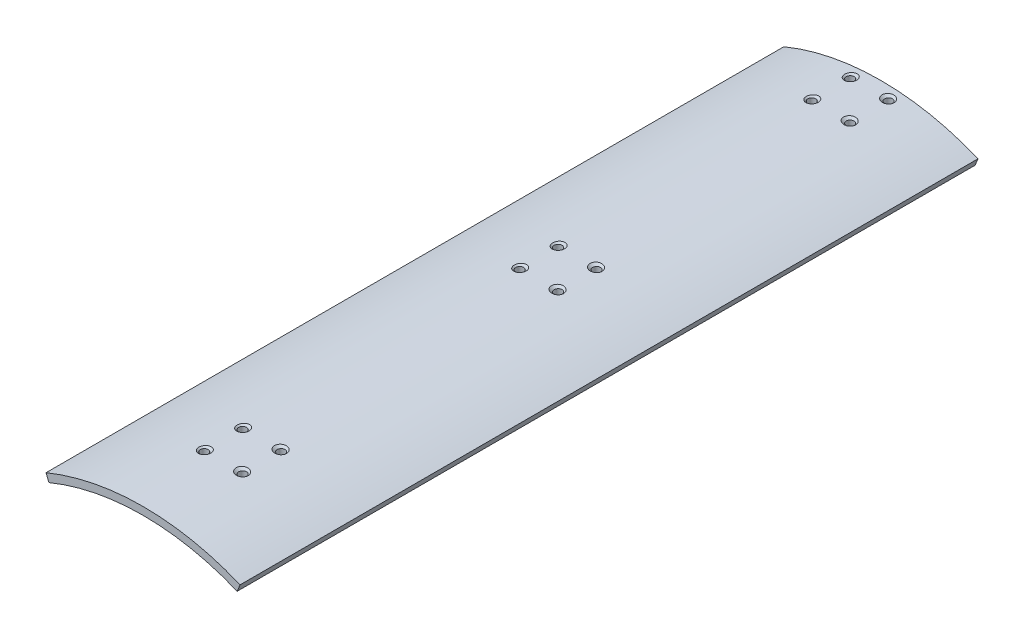
SolidWorks part; units mm, degrees
ref_plane "Front Plane" through (0, 0, 0) normal (0, 0, 1) x (1, 0, 0)
ref_plane "Top Plane" through (0, 0, 0) normal (0, 1, 0) x (1, 0, 0)
ref_plane "Right Plane" through (0, 0, 0) normal (1, 0, 0) x (0, 0, -1)
sketch "Sketch1" plane through (0, 0, 0) normal (0, 0, 1) x (1, 0, 0)
  line L0 (-40.0957, 96.7995) -> (-38.8806, 93.8662)
  line L2 (40.0957, 96.7995) -> (38.8806, 93.8662)
  arc A0 (-40.0957, 96.7995) -> (40.0957, 96.7995) centre (0, 0) cw
  arc A2 (-38.8806, 93.8662) -> (38.8806, 93.8662) centre (0, 0) cw
extrude "Boss-Extrude1" add sketch "Sketch1" along normal blind 152.4 and the other way blind 152.4
sketch "Sketch2" plane through (0, 0, 152.4) normal (0, 0, 1) x (1, 0, 0)
  arc A0 (40.0957, 96.7995) -> (-40.0957, 96.7995) centre (0, 0) ccw construction
  point P0 (7.9707, 104.4714)
ref_plane "Plane1" through (0, 104.4714, 0) normal (0, 1, 0) x (1, 0, 0)
sketch "Sketch3" plane through (0, 104.4714, 0) normal (0, 1, 0) x (1, 0, 0)
  line L0 (40.0957, 152.4) -> (-40.0957, 152.4) construction
  line L1 (0, -5.9999) -> (0, 5.9999) construction
  circle A0 centre (7.9375, 26.9875) radius 2.8448
  circle A1 centre (7.9375, 11.1125) radius 2.8448
  circle A2 centre (-7.9375, 26.9875) radius 2.8448
  circle A3 centre (-7.9375, 11.1125) radius 2.8448
  circle A4 centre (7.9375, -103.3145) radius 2.8448
  circle A5 centre (7.9375, -119.1895) radius 2.8448
  circle A6 centre (-7.9375, -119.1895) radius 2.8448
  circle A7 centre (-7.9375, -103.3145) radius 2.8448
  circle A8 centre (7.9375, 147.6375) radius 2.8448
  circle A9 centre (7.9375, 131.7625) radius 2.8448
  circle A10 centre (-7.9375, 131.7625) radius 2.8448
  circle A11 centre (-7.9375, 147.6375) radius 2.8448
  dimension "D1" = 125.4125
  dimension "D2" = 15.875
  dimension "D5" = 7.9375
  dimension "D3" = 15.875
  dimension "D4" = 7.9375
  dimension "D6" = 2
  dimension "D7" = 2
ref_plane "Plane2" through (0, 104.775, 0) normal (0, 1, 0) x (1, 0, 0)
sketch "Sketch9" plane through (0, 104.775, 0) normal (0, 1, 0) x (1, 0, 0)
  line L0 (40.0957, 152.4) -> (-40.0957, 152.4) construction
  line L1 (0, -5.9999) -> (0, 5.9999) construction
  circle A0 centre (7.9375, 26.9875) radius 2.8448
  circle A1 centre (-7.9375, 26.9875) radius 2.8448
  circle A2 centre (7.9375, 11.1125) radius 2.8448
  circle A3 centre (-7.9375, 11.1125) radius 2.8448
  circle A4 centre (7.9375, -119.1895) radius 2.8448
  circle A5 centre (-7.9375, -119.1895) radius 2.8448
  circle A6 centre (-7.9375, -103.3145) radius 2.8448
  circle A7 centre (7.9375, -103.3145) radius 2.8448
  circle A8 centre (7.9375, 131.7625) radius 2.8448
  circle A9 centre (-7.9375, 131.7625) radius 2.8448
  circle A10 centre (-7.9375, 147.6375) radius 2.8448
  circle A11 centre (7.9375, 147.6375) radius 2.8448
  dimension "D1" = 125.4125
  dimension "D3" = 7.9375
  dimension "D5" = 2
  dimension "D2" = 7.9375
  dimension "D4" = 15.875
  dimension "D6" = 2
hole_wizard "CSK for #4 Flat Head Machine Screw (100)2" positions "Sketch11" profile "Sketch10" countersink size "#4" standard "ANSI Inch" end condition through all
sketch "Sketch11" plane through (0, 104.775, 0) normal (0, 1, 0) x (1, 0, 0)
  point P0 (7.9375, 147.6375)
  point P3 (7.9375, 131.7625)
  point P6 (-7.9375, 131.7625)
  point P9 (-7.9375, 147.6375)
  point P12 (7.9375, 26.9875)
  point P15 (7.9375, 11.1125)
  point P18 (-7.9375, 11.1125)
  point P21 (-7.9375, 26.9875)
  point P24 (7.9375, -103.3145)
  point P27 (7.9375, -119.1895)
  point P30 (-7.9375, -119.1895)
  point P33 (-7.9375, -103.3145)
sketch "Sketch10" plane through (7.9375, 104.775, -147.6375) normal (1, 0, 0) x (0, 0, 1)
  line L0 (0, 0) -> (0, 10.9088)
  line L1 (0, 10.9088) -> (1.6319, 10.9088)
  line L2 (1.6319, 10.9088) -> (1.6319, 1.0284)
  line L3 (1.6319, 1.0284) -> (2.8575, 0)
  line L5 (2.8575, 0) -> (0, 0)
  line L6 (-1.6319, 1.0284) -> (-2.8575, 0) construction
  line L11 (0, -6.35) -> (0, 107.95) construction
  dimension "Thru Hole Dia." = 3.2639
  dimension "Thru Hole Depth" = 10.9088
  dimension "Near C'Sink Dia." = 5.715
  dimension "Near C'Sink Angle" = 100
